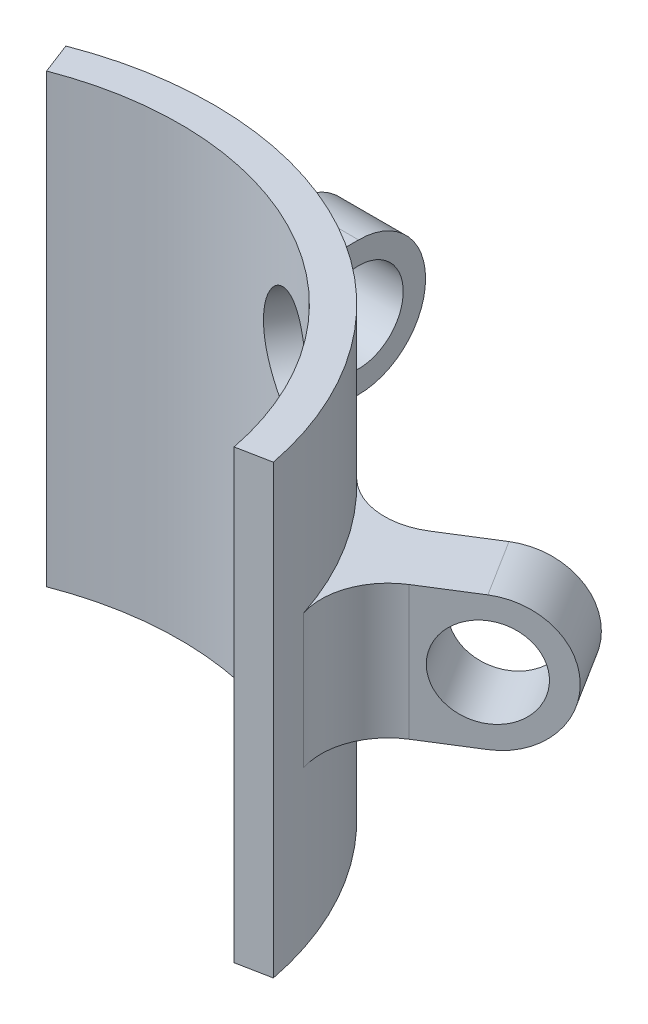
SolidWorks part; units mm, degrees
ref_plane "Front Plane" through (0, 0, 0) normal (0, 0, 1) x (1, 0, 0)
ref_plane "Top Plane" through (0, 0, 0) normal (0, 1, 0) x (1, 0, 0)
ref_plane "Right Plane" through (0, 0, 0) normal (1, 0, 0) x (0, 0, -1)
sketch "Sketch2" plane through (0, 0, 0) normal (0, 1, 0) x (1, 0, 0)
  circle A0 centre (0, 0) radius 14
  circle A1 centre (0, 0) radius 15.5
  dimension "D1" = 28
  dimension "D2" = 1.5
extrude "Boss-Extrude1" add sketch "Sketch2" along normal blind 20
sketch "Sketch3" plane through (0, 20, 0) normal (0, 1, 0) x (1, 0, 0)
  line L0 (0, 0) -> (7.5, 13.5647)
  line L1 (0, 0) -> (-7.5, 13.5647)
  line L2 (7.5, 13.5647) -> (-7.5, 13.5647) construction
  circle A0 centre (0, 0) radius 15.5 construction
  arc A1 (7.5, 13.5647) -> (-7.5, 13.5647) centre (0, 0) ccw
  point P6 (0, 15.5)
  dimension "D1" = 15
extrude "Cut-Extrude1" cut sketch "Sketch3" against normal through all flip side to cut
ref_plane "Plane1" through (0, 10, 0) normal (0, 1, 0) x (1, 0, 0)
sketch "Sketch6" plane through (0, 7.5, 0) normal (-1, 0, 0) x (0, 1, 0)
  line L0 (-0.5, 20.5) -> (-0.5, 15.25)
  line L1 (5.5, 20.5) -> (5.5, 15.25)
  line L2 (12.5, 15.5) -> (-7.5, 15.5) construction
  line L3 (12.5, 12.252) -> (-7.5, 12.252) construction
  line L4 (-0.5, 15.25) -> (5.5, 15.25)
  line L5 (12.5, 15.5) -> (-7.5, 15.5) construction
  circle A0 centre (2.5, 20.5) radius 2
  arc A1 (5.5, 20.5) -> (-0.5, 20.5) centre (2.5, 20.5) ccw
  point P10 (2.5, 12.252)
  dimension "D1" = 4
  dimension "D2" = 1
  dimension "D4" = 5
  dimension "D3" = 0.25
extrude "Boss-Extrude2" add sketch "Sketch6" along normal blind 1.5 and the other way blind 1.5
mirror "Mirror2" about plane through (0, 0, 0) normal (0.8751, 0, 0.4839) of "Boss-Extrude2", "Boss-Extrude1"
sketch "Sketch8" plane through (0, 0, 0) normal (0, 1, 0) x (1, 0, 0)
  line L0 (-5.5702, 14.4645) -> (0, 0)
  line L1 (0, 0) -> (15.212, 2.9739)
  line L2 (-5.5702, 14.4645) -> (-1.5, 23.5) construction
  line L3 (0, 15.5) -> (-5.5702, 14.4645) construction
  line L4 (20.7, 11.2255) -> (15.212, 2.9739) construction
  line L5 (13.1271, 8.2419) -> (15.212, 2.9739) construction
  arc A0 (-5.5702, 14.4645) -> (15.212, 2.9739) centre (0, 0) ccw
  circle A1 centre (0, 0) radius 15.5 construction
  arc A2 (1.5, 15.4272) -> (-1.5, 15.4272) centre (0, 0) ccw construction
  arc A3 (13.8631, 6.9329) -> (12.2679, 9.4736) centre (0, 0) ccw construction
  dimension "D1" = 100
extrude "Cut-Extrude4" cut sketch "Sketch8" against normal blind 10 and the other way through all contours L1 A0 L0
ref_plane "Plane2" through (4.3544, 0, -7.8754) normal (0.4839, 0, -0.8751) x (-0.8751, 0, -0.4839)
sketch "Sketch9" plane through (4.3544, 0, -7.8754) normal (0.4839, 0, -0.8751) x (-0.8751, 0, -0.4839)
  line L0 (0, 15) -> (0, 20) construction
  line L1 (11.8737, 20) -> (-11.8737, 20) construction
  line L2 (0, 5) -> (0, 0) construction
  circle A0 centre (0, 15) radius 2.5
  circle A1 centre (0, 5) radius 2.5
  dimension "D1" = 5
  dimension "D2" = 5
extrude "Cut-Extrude5" cut sketch "Sketch9" along normal blind 10
fillet "Fillet1" radius 3 4 edges at (13.8631, 10, -6.9329) (-1.5, 10, -15.4272) (1.5, 10, -15.4272) (12.2679, 10, -9.4736)
equation "\"keelOutDiameter\"= 1in"
equation "\"poleOutDiameter\"= 28mm"
equation "\"poleLength\"=650mm"
equation "\"propellerTubeOutDiameter\"= 28mm"
equation "\"propellerDiameter\"= 700mm"
equation "\"D1@Sketch2\"=\"poleOutDiameter\""
